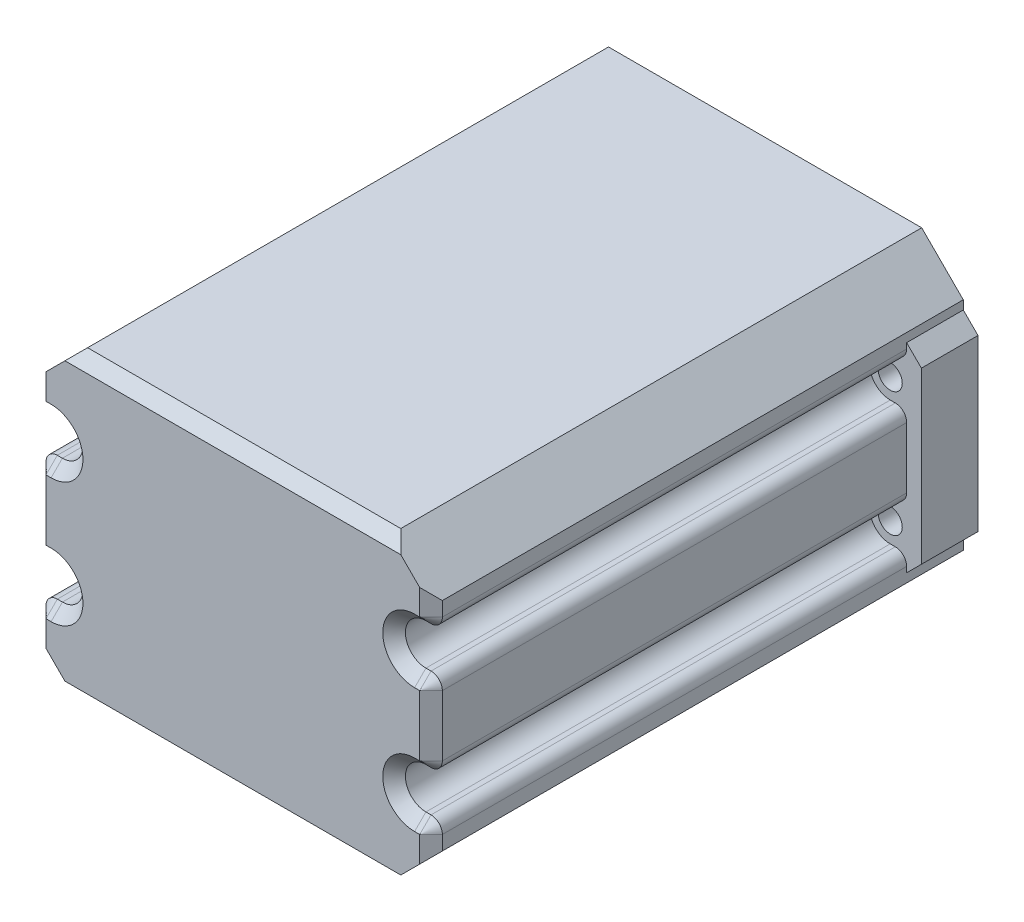
SolidWorks part; units mm, degrees
note: The reader was unsure of these and kept them because the rebuilt part matched: shared geometry of "Sketch1<3>".
ref_plane "Front Plane" through (0, 0, 0) normal (0, 0, 1) x (1, 0, 0)
ref_plane "Top Plane" through (0, 0, 0) normal (0, 1, 0) x (1, 0, 0)
ref_plane "Right Plane" through (0, 0, 0) normal (1, 0, 0) x (0, 0, -1)
sketch "Sketch1" plane through (0, 0, 0) normal (0, 0, 1) x (1, 0, 0)
  line L0 (27.6569, 53) -> (27.6569, 0) construction
  line L2 (-3.3431, 9.6017) -> (-3.3431, 9)
  line L4 (-4.4431, 41.125) -> (-7.3431, 41.125)
  line L5 (-4.4431, 33.875) -> (-7.3431, 33.875)
  line L6 (-4.4431, 11.875) -> (-7.3431, 11.875)
  line L7 (-4.4431, 19.125) -> (-7.3431, 19.125)
  line L8 (-7.3431, 41.5) -> (-9.9431, 41.5)
  line L13 (-9.9431, 41.5) -> (-9.9431, 11.5)
  line L17 (55.3137, 53) -> (0, 53)
  line L18 (0, 53) -> (-7.3431, 45.6569)
  line L19 (-7.3431, 45.6569) -> (-7.3431, 41.125)
  line L20 (-7.3431, 7.3431) -> (0, 0)
  line L21 (0, 0) -> (55.3137, 0)
  line L28 (-7.3431, 11.875) -> (-7.3431, 7.3431)
  line L29 (-7.3431, 33.875) -> (-7.3431, 19.125)
  line L30 (-7.3431, 33.875) -> (-7.3431, 19.125)
  line L33 (27.6569, 49) -> (1.6569, 49)
  line L37 (1.6569, 4) -> (27.6569, 4)
  line L38 (-3.3431, 9) -> (1.6569, 4)
  line L44 (1.5569, 37.5) -> (1.5569, 15.5)
  line L46 (1.6569, 49) -> (-3.3431, 44)
  line L47 (-3.3431, 44) -> (-3.3431, 43.3983)
  line L50 (-9.9431, 11.5) -> (-7.3431, 11.5)
  line L57 (65.2569, 11.5) -> (62.6569, 11.5)
  line L58 (58.6569, 44) -> (58.6569, 43.3983)
  line L59 (53.6569, 49) -> (58.6569, 44)
  line L60 (53.7569, 37.5) -> (53.7569, 15.5)
  line L61 (58.6569, 9) -> (53.6569, 4)
  line L62 (53.6569, 4) -> (27.6569, 4)
  line L63 (27.6569, 49) -> (53.6569, 49)
  line L64 (62.6569, 33.875) -> (62.6569, 19.125)
  line L66 (62.6569, 33.875) -> (62.6569, 19.125)
  line L67 (62.6569, 11.875) -> (62.6569, 7.3431)
  line L68 (62.6569, 7.3431) -> (55.3137, 0)
  line L70 (62.6569, 45.6569) -> (62.6569, 41.125)
  line L71 (55.3137, 53) -> (62.6569, 45.6569)
  line L72 (65.2569, 41.5) -> (65.2569, 11.5)
  line L73 (62.6569, 41.5) -> (65.2569, 41.5)
  line L74 (59.7569, 19.125) -> (62.6569, 19.125)
  line L75 (59.7569, 11.875) -> (62.6569, 11.875)
  line L76 (59.7569, 33.875) -> (62.6569, 33.875)
  line L77 (59.7569, 41.125) -> (62.6569, 41.125)
  line L78 (58.6569, 9.6017) -> (58.6569, 9)
  line L79 (-9.9431, 41.5) -> (-9.9431, 11.5) construction
  line L80 (-9.9431, 41.5) -> (-7.3431, 44.1)
  line L81 (-9.9431, 11.5) -> (-7.3431, 8.9)
  line L82 (-7.3431, 8.9) -> (-7.3431, 11.5)
  line L83 (-7.3431, 44.1) -> (-7.3431, 41.5)
  line L84 (62.6569, 41.5) -> (65.2569, 41.5)
  line L85 (65.2569, 41.5) -> (62.6569, 44.1)
  line L86 (65.2569, 41.5) -> (62.6569, 44.1) construction
  line L87 (62.6569, 44.1) -> (62.6569, 41.5)
  line L88 (65.2569, 11.5) -> (62.6569, 8.9)
  line L89 (62.6569, 8.9) -> (65.2569, 11.5) construction
  line L90 (62.6569, 8.9) -> (62.6569, 11.5)
  arc A0 (-4.4431, 33.875) -> (-4.4431, 41.125) centre (-4.4431, 37.5) ccw
  circle A1 centre (-4.4431, 15.5) radius 2.125
  circle A4 centre (-4.4431, 37.5) radius 2.125
  arc A5 (-4.4431, 11.875) -> (-4.4431, 19.125) centre (-4.4431, 15.5) ccw
  arc A14 (58.6569, 9.6017) -> (53.7569, 15.5) centre (59.7569, 15.5) cw
  arc A26 (1.5569, 37.5) -> (-3.3431, 43.3983) centre (-4.4431, 37.5) ccw
  arc A27 (-3.3431, 9.6017) -> (1.5569, 15.5) centre (-4.4431, 15.5) ccw
  arc A28 (53.7569, 37.5) -> (58.6569, 43.3983) centre (59.7569, 37.5) cw
  arc A29 (59.7569, 11.875) -> (59.7569, 19.125) centre (59.7569, 15.5) cw
  circle A30 centre (59.7569, 37.5) radius 2.125
  circle A31 centre (59.7569, 15.5) radius 2.125
  arc A32 (59.7569, 33.875) -> (59.7569, 41.125) centre (59.7569, 37.5) cw
  point P43 (14.6569, 4)
  point P44 (14.6569, 49)
  point P63 (40.6569, 49)
  point P64 (40.6569, 4)
  point P75 (1.5569, 26.5)
  point P76 (27.6569, 26.5)
  dimension "D3" = 7.25
  dimension "D4" = 4.25
  dimension "D5" = 12
  dimension "D6" = 22
  dimension "D7" = 32.1
  dimension "D1" = 45
  dimension "D2" = 45
  dimension "D8" = 4
  dimension "D9" = 45
  dimension "D10" = 5
  dimension "D11" = 4
  dimension "D12" = 4
  dimension "D13" = 4
  dimension "D14" = 5
  dimension "D15" = 4
  dimension "D16" = 31
extrude "Boss-Extrude1" add sketch "Sketch1" along normal blind 90
extrude "Boss-Extrude2" add sketch "Sketch1<3>" along normal blind 10
sketch "Sketch1<3>" plane through (0, 0, 0) normal (0, 0, 1) x (1, 0, 0) same geometry as "Sketch1"
fillet "Fillet1" radius 2 8 edges at (-7.3431, 41.125, 50) (-7.3431, 19.125, 50) (-7.3431, 11.875, 50) (-7.3431, 33.875, 50) (62.6569, 41.125, 50) (62.6569, 33.875, 50) (62.6569, 19.125, 50) (62.6569, 11.875, 50)
sketch "Sketch2" plane through (0, 0, 90) normal (0, 0, 1) x (1, 0, 0)
  line L21 (-7.3431, 31.875) -> (-7.3431, 21.125)
  line L28 (-7.3431, 9.875) -> (-7.3431, 7.3431)
  line L37 (55.3137, 0) -> (62.6569, 7.3431)
  line L43 (55.3137, 53) -> (0, 53)
  line L44 (0, 53) -> (-7.3431, 45.6569)
  line L45 (-7.3431, 45.6569) -> (-7.3431, 43.125)
  line L46 (-5.3431, 41.125) -> (-4.4431, 41.125)
  line L47 (-4.4431, 33.875) -> (-5.3431, 33.875)
  line L49 (-5.3431, 19.125) -> (-4.4431, 19.125)
  line L50 (-4.4431, 11.875) -> (-5.3431, 11.875)
  line L52 (-7.3431, 7.3431) -> (0, 0)
  line L53 (0, 0) -> (55.3137, 0)
  line L72 (62.6569, 7.3431) -> (62.6569, 9.875)
  line L82 (60.6569, 11.875) -> (59.7569, 11.875)
  line L86 (59.7569, 19.125) -> (60.6569, 19.125)
  line L90 (62.6569, 21.125) -> (62.6569, 31.875)
  line L92 (60.6569, 33.875) -> (59.7569, 33.875)
  line L94 (59.7569, 41.125) -> (60.6569, 41.125)
  line L96 (62.6569, 43.125) -> (62.6569, 45.6569)
  line L98 (62.6569, 45.6569) -> (55.3137, 53)
  arc A12 (59.7569, 19.125) -> (59.7569, 11.875) centre (59.7569, 15.5) ccw
  arc A15 (59.7569, 41.125) -> (59.7569, 33.875) centre (59.7569, 37.5) ccw
  arc A18 (-7.3431, 43.125) -> (-5.3431, 41.125) centre (-5.3431, 43.125) ccw
  arc A23 (-5.3431, 33.875) -> (-7.3431, 31.875) centre (-5.3431, 31.875) ccw
  arc A31 (-7.3431, 21.125) -> (-5.3431, 19.125) centre (-5.3431, 21.125) ccw
  arc A35 (-5.3431, 11.875) -> (-7.3431, 9.875) centre (-5.3431, 9.875) ccw
  arc A46 (-4.4431, 33.875) -> (-4.4431, 41.125) centre (-4.4431, 37.5) ccw
  arc A49 (-4.4431, 11.875) -> (-4.4431, 19.125) centre (-4.4431, 15.5) ccw
  arc A62 (60.6569, 41.125) -> (62.6569, 43.125) centre (60.6569, 43.125) ccw
  arc A64 (62.6569, 9.875) -> (60.6569, 11.875) centre (60.6569, 9.875) ccw
  arc A66 (60.6569, 19.125) -> (62.6569, 21.125) centre (60.6569, 21.125) ccw
  arc A68 (62.6569, 31.875) -> (60.6569, 33.875) centre (60.6569, 31.875) ccw
extrude "Boss-Extrude3" add sketch "Sketch2" along normal blind 4
chamfer "Chamfer1" distance 2 angle 45 28 edges at (27.6569, 0, 94) (27.6569, 53, 94) (-4.8931, 11.875, 94) (-0.8181, 15.5, 94) (-4.8931, 19.125, 94) (-7.3431, 44.3909, 94) (-7.3431, 26.5, 94) (-7.3431, 8.6091, 94) (-6.7574, 41.7108, 94) (-4.8931, 41.125, 94) (-4.8931, 33.875, 94) (-0.8181, 37.5, 94) (-6.7574, 11.2892, 94) (-6.7574, 19.7108, 94) (-6.7574, 33.2892, 94) (62.6569, 8.6091, 94) (62.6569, 44.3909, 94) (62.0711, 11.2892, 94) (62.0711, 41.7108, 94) (60.2069, 11.875, 94) (60.2069, 41.125, 94) (56.1319, 15.5, 94) (56.1319, 37.5, 94) (60.2069, 19.125, 94) (60.2069, 33.875, 94) (62.0711, 19.7108, 94) (62.0711, 33.2892, 94) (62.6569, 26.5, 94)
sketch "Sketch3" plane through (0, 0, 0) normal (0, 0, -1) x (-1, 0, 0)
  line L0 (-54.0711, 50) -> (-59.6569, 44.4142)
  line L1 (-59.6569, 44.4142) -> (-59.6569, 42.499)
  line L2 (-54.7569, 37.5) -> (-54.7569, 15.5)
  line L3 (-59.6569, 10.501) -> (-59.6569, 8.5858)
  line L4 (-59.6569, 8.5858) -> (-54.0711, 3)
  line L5 (-54.0711, 3) -> (-1.2426, 3)
  line L6 (-1.2426, 3) -> (4.3431, 8.5858)
  line L7 (4.3431, 8.5858) -> (4.3431, 10.501)
  line L8 (-0.5569, 15.5) -> (-0.5569, 37.5)
  line L9 (4.3431, 42.499) -> (4.3431, 44.4142)
  line L10 (4.3431, 44.4142) -> (-1.2426, 50)
  line L11 (-1.2426, 50) -> (-54.0711, 50)
  line L12 (-1.6569, 49) -> (-53.6569, 49)
  line L13 (3.3431, 44) -> (-1.6569, 49)
  line L14 (3.3431, 43.3983) -> (3.3431, 44)
  line L15 (-1.5569, 15.5) -> (-1.5569, 37.5)
  line L16 (3.3431, 9) -> (3.3431, 9.6017)
  line L17 (-1.6569, 4) -> (3.3431, 9)
  line L18 (-53.6569, 4) -> (-1.6569, 4)
  line L19 (-58.6569, 9) -> (-53.6569, 4)
  line L20 (-58.6569, 9.6017) -> (-58.6569, 9)
  line L21 (-53.7569, 37.5) -> (-53.7569, 15.5)
  line L22 (-58.6569, 44) -> (-58.6569, 43.3983)
  line L23 (-53.6569, 49) -> (-58.6569, 44)
  line L24 (-1.6569, 49) -> (-53.6569, 49)
  line L25 (3.3431, 44) -> (-1.6569, 49)
  line L26 (3.3431, 43.3983) -> (3.3431, 44)
  line L27 (-1.5569, 15.5) -> (-1.5569, 37.5)
  line L28 (3.3431, 9) -> (3.3431, 9.6017)
  line L29 (-1.6569, 4) -> (3.3431, 9)
  line L30 (-53.6569, 4) -> (-1.6569, 4)
  line L31 (-58.6569, 9) -> (-53.6569, 4)
  line L32 (-58.6569, 9.6017) -> (-58.6569, 9)
  line L33 (-53.7569, 37.5) -> (-53.7569, 15.5)
  line L34 (-58.6569, 44) -> (-58.6569, 43.3983)
  line L35 (-53.6569, 49) -> (-58.6569, 44)
  line L36 (-54.8995, 52) -> (-61.6569, 45.2426)
  line L37 (-61.6569, 45.2426) -> (-61.6569, 39.8216)
  line L38 (-56.7569, 37.5) -> (-56.7569, 15.5)
  line L39 (-61.6569, 13.1784) -> (-61.6569, 7.7574)
  line L40 (-61.6569, 7.7574) -> (-54.8995, 1)
  line L41 (-54.8995, 1) -> (-0.4142, 1)
  line L42 (-0.4142, 1) -> (6.3431, 7.7574)
  line L43 (6.3431, 7.7574) -> (6.3431, 13.1784)
  line L44 (1.4431, 15.5) -> (1.4431, 37.5)
  line L45 (6.3431, 39.8216) -> (6.3431, 45.2426)
  line L46 (6.3431, 45.2426) -> (-0.4142, 52)
  line L47 (-0.4142, 52) -> (-54.8995, 52)
  arc A0 (-54.7569, 37.5) -> (-59.6569, 42.499) centre (-59.7569, 37.5) ccw
  circle A1 centre (4.4431, 15.5) radius 2.125
  circle A2 centre (4.4431, 15.5) radius 2.125
  circle A3 centre (4.4431, 37.5) radius 2.125
  arc A4 (3.3431, 43.3983) -> (-1.5569, 37.5) centre (4.4431, 37.5) ccw
  arc A5 (-1.5569, 15.5) -> (3.3431, 9.6017) centre (4.4431, 15.5) ccw
  arc A6 (-58.6569, 9.6017) -> (-53.7569, 15.5) centre (-59.7569, 15.5) ccw
  arc A7 (-53.7569, 37.5) -> (-58.6569, 43.3983) centre (-59.7569, 37.5) ccw
  arc A8 (3.3431, 43.3983) -> (-1.5569, 37.5) centre (4.4431, 37.5) ccw
  arc A9 (-1.5569, 15.5) -> (3.3431, 9.6017) centre (4.4431, 15.5) ccw
  arc A10 (-58.6569, 9.6017) -> (-53.7569, 15.5) centre (-59.7569, 15.5) ccw
  arc A11 (-53.7569, 37.5) -> (-58.6569, 43.3983) centre (-59.7569, 37.5) ccw
  circle A12 centre (4.4431, 37.5) radius 2.125
  circle A13 centre (-59.7569, 37.5) radius 2.125
  circle A14 centre (-59.7569, 37.5) radius 2.125
  circle A15 centre (-59.7569, 15.5) radius 2.125
  circle A16 centre (-59.7569, 15.5) radius 2.125
  arc A17 (-59.6569, 10.501) -> (-54.7569, 15.5) centre (-59.7569, 15.5) ccw
  arc A18 (-0.5569, 15.5) -> (4.3431, 10.501) centre (4.4431, 15.5) ccw
  arc A19 (4.3431, 42.499) -> (-0.5569, 37.5) centre (4.4431, 37.5) ccw
  arc A20 (-56.7569, 37.5) -> (-61.6569, 39.8216) centre (-59.7569, 37.5) ccw
  arc A21 (-61.6569, 13.1784) -> (-56.7569, 15.5) centre (-59.7569, 15.5) ccw
  arc A22 (1.4431, 15.5) -> (6.3431, 13.1784) centre (4.4431, 15.5) ccw
  arc A23 (6.3431, 39.8216) -> (1.4431, 37.5) centre (4.4431, 37.5) ccw
  dimension "D1" = 0
  dimension "D2" = 0
  dimension "D3" = 0
  dimension "D4" = 0
  dimension "D5" = 0
  dimension "D6" = 1
  dimension "D7" = 2
extrude "Cut-Extrude1" cut sketch "Sketch3" against normal blind 1.7 contours A23 L45 L46 L47 L36 L37 A20 L38 A21 L39 L40 L41 L42 L43 A22 L44 L9 A19 L8 A18 L7 L6 L5 L4 L3 A17 L2 A0 L1 L0 L11 L10
fillet "Fillet2" radius 2 12 edges at (1.2426, 3, 0.85) (-4.3431, 8.5858, 0.85) (-4.3431, 10.501, 0.85) (-4.3431, 42.499, 0.85) (-4.3431, 44.4142, 0.85) (1.2426, 50, 0.85) (54.0711, 50, 0.85) (59.6569, 44.4142, 0.85) (59.6569, 42.499, 0.85) (54.0711, 3, 0.85) (59.6569, 8.5858, 0.85) (59.6569, 10.501, 0.85)
